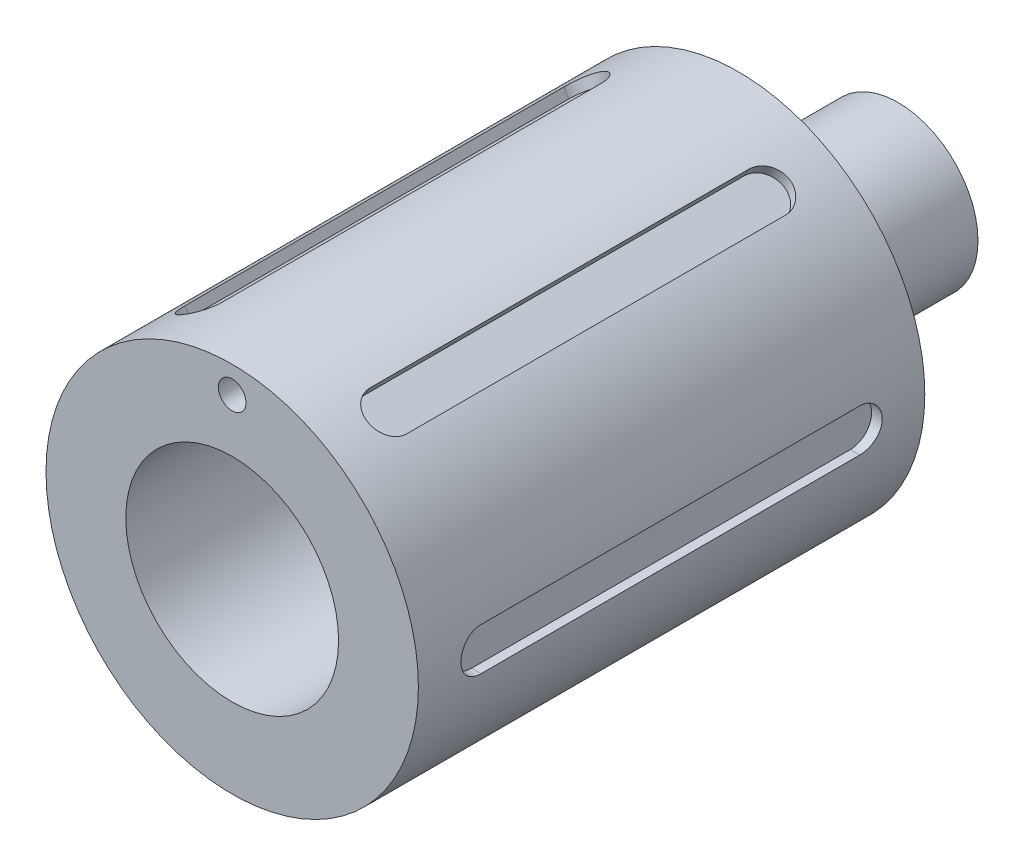
SolidWorks part; units mm, degrees
material "Plain Carbon Steel"
ref_plane "Front Plane" through (0, 0, 0) normal (0, 0, 1) x (1, 0, 0)
ref_plane "Top Plane" through (0, 0, 0) normal (0, 1, 0) x (1, 0, 0)
ref_plane "Right Plane" through (0, 0, 0) normal (1, 0, 0) x (0, 0, -1)
ref_axis "X-axis" through (-88.99, 0, 0) along (1, 0, 0)
ref_axis "Y-axis" through (0, 55, 0) along (0, -1, 0)
ref_axis "Z-axis" through (0, 0, -88.99) along (0, 0, 1)
sketch "Sketch1" plane through (0, 0, 0) normal (1, 0, 0) x (0, 0, -1)
  line L0 (0, 0) -> (46.9363, 0) construction
  line L1 (0, 0) -> (-79.502, 0)
  line L2 (-79.502, 0) -> (-79.502, 22.225)
  line L3 (-79.502, 22.225) -> (-19.05, 22.225)
  line L4 (-19.05, 22.225) -> (-19.05, 9.525)
  line L5 (-19.05, 9.525) -> (0, 9.525)
  line L6 (0, 9.525) -> (0, 0)
  dimension "D1" = 60.452
  dimension "D2" = 19.05
  dimension "D3" = 44.45
  dimension "D4" = 19.05
revolve "Revolve1" add sketch "Sketch1" angle 360 about L0
hole_wizard "1/4 (1) Diameter Hole1" positions "Sketch2" profile "Sketch4" hole size "1/4" standard "ANSI Inch"
sketch "Sketch2" plane through (0, 0, 79.502) normal (0, 0, 1) x (1, 0, 0)
  point P0 (0, 0)
sketch "Sketch4" plane through (0, 0, 79.502) normal (1, 0, 0) x (0, -1, 0)
  line L0 (0, 0) -> (0, 57.15)
  line L1 (0, 57.15) -> (12.7, 57.15)
  line L2 (12.7, 57.15) -> (12.7, 0)
  line L5 (12.7, 0) -> (0, 0)
  line L10 (0, 57.15) -> (-12.7, 57.15) construction
  line L11 (0, -6.35) -> (0, 107.95) construction
  dimension "Hole Dia." = 25.4
  dimension "Hole Depth" = 57.15
  dimension "Drill Angle" = 180
hole_wizard "1/4 (0.13) Diameter Hole1" positions "Sketch5" profile "Sketch6" hole size "1/4" standard "ANSI Inch"
sketch "Sketch5" plane through (0, 0, 79.502) normal (0, 0, 1) x (1, 0, 0)
  point P0 (0, 19.05)
  dimension "D1" = 19.05
sketch "Sketch6" plane through (0, 19.05, 79.502) normal (1, 0, 0) x (0, -1, 0)
  line L0 (0, 0) -> (0, 16.867)
  line L1 (0, 16.867) -> (1.651, 15.875)
  line L2 (1.651, 15.875) -> (1.651, 0)
  line L5 (1.651, 0) -> (0, 0)
  line L10 (0, 16.867) -> (-1.651, 15.875) construction
  line L11 (0, -6.35) -> (0, 107.95) construction
  dimension "Hole Dia." = 3.302
  dimension "Hole Depth" = 15.875
  dimension "Drill Angle" = 118
ref_plane "Plane2" through (22.225, 0, 0) normal (1, 0, 0) x (0, 0, -1)
sketch "Sketch10" plane through (22.225, 0, 0) normal (1, 0, 0) x (0, 0, -1)
  line L0 (-71.882, 0) -> (-26.67, 0) construction
  line L1 (-71.882, 2.54) -> (-26.67, 2.54)
  line L2 (-71.882, -2.54) -> (-26.67, -2.54)
  line L3 (-79.502, 22.225) -> (-79.502, -22.225) construction
  arc A0 (-71.882, 2.54) -> (-71.882, -2.54) centre (-71.882, 0) ccw
  arc A1 (-26.67, -2.54) -> (-26.67, 2.54) centre (-26.67, 0) ccw
  point P2 (-49.276, 0)
  dimension "D1" = 45.212
  dimension "D2" = 7.62
  dimension "D3" = 5.08
extrude "Cut-Extrude2" cut sketch "Sketch10" against normal blind 1.27
pattern_circular "CirPattern2" count 6 over 360 about axis through (0, 0, 0) along (0, 0, 1) of "Cut-Extrude2" reverse direction yes
